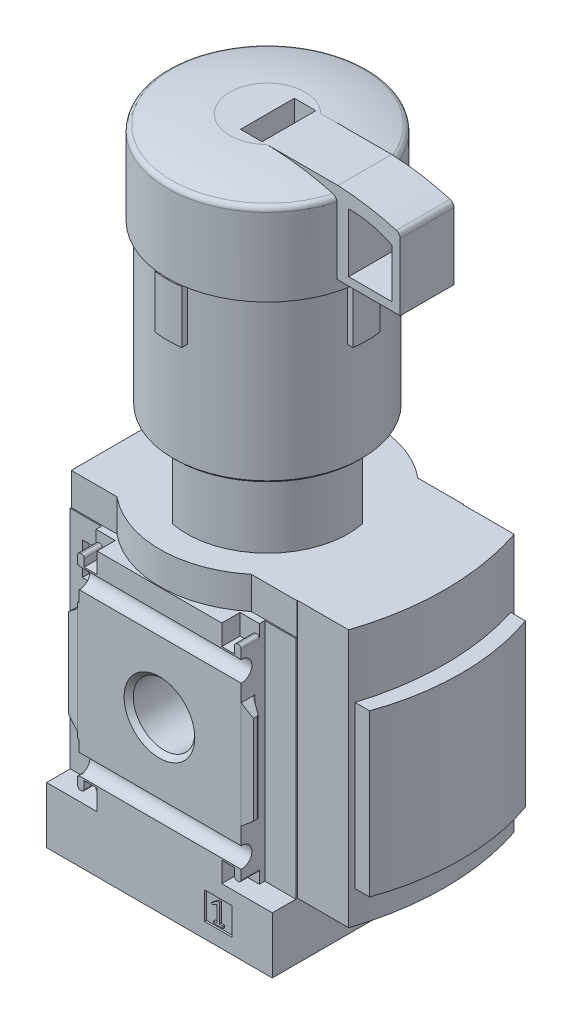
SolidWorks part; units mm, degrees
ref_plane "Front Plane" through (0, 0, 0) normal (0, 0, 1) x (1, 0, 0)
ref_plane "Top Plane" through (0, 0, 0) normal (0, 1, 0) x (1, 0, 0)
ref_plane "Right Plane" through (0, 0, 0) normal (1, 0, 0) x (0, 0, -1)
ref_plane "Plane1" through (0, 27, 0) normal (0, 1, 0) x (1, 0, 0)
sketch "Sketch1" plane through (0, 27, 0) normal (0, 1, 0) x (1, 0, 0)
  line L0 (-21, -15.5) -> (-12.5, -15.5)
  line L1 (12.5, -15.5) -> (21, -15.5)
  line L2 (21, -15.5) -> (21, 15.5)
  line L3 (21, 15.5) -> (12.5, 15.5)
  line L4 (-12.5, 15.5) -> (-21, 15.5)
  line L5 (-21, 15.5) -> (-21, -15.5)
  arc A0 (-12.5, -15.5) -> (12.5, -15.5) centre (0, -0.3889) ccw
  arc A1 (12.5, 15.5) -> (-12.5, 15.5) centre (0, 0.3889) ccw
extrude "Boss-Extrude1" add sketch "Sketch1" against normal blind 48
sketch "Sketch2" plane through (0, 0, 0) normal (0, 0, 1) x (1, 0, 0)
  line L0 (-21, -21) -> (21, -21)
  line L1 (21, -21) -> (21, 21)
  line L2 (21, 21) -> (-21, 21)
  line L3 (-21, 21) -> (-21, -21)
extrude "Boss-Extrude2" add sketch "Sketch2" against normal blind 20.1 and the other way blind 20.1
ref_plane "Plane2" through (0, -31, 0) normal (0, 1, 0) x (1, 0, 0)
ref_plane "Plane3" through (0, -31.5, 0) normal (0, 1, 0) x (1, 0, 0)
sketch "Sketch3" plane through (0, -31.5, 0) normal (0, 1, 0) x (1, 0, 0)
  line L0 (-21, -20.1) -> (21, -20.1)
  line L1 (21, -20.1) -> (21, 20.1)
  line L2 (21, 20.1) -> (-21, 20.1)
  line L3 (-21, 20.1) -> (-21, -20.1)
extrude "Boss-Extrude3" add sketch "Sketch3" along normal blind 10.5
ref_plane "Plane4" through (0, 27, 0) normal (0, 1, 0) x (1, 0, 0)
sketch "Sketch4" plane through (0, 0, 0) normal (1, 0, 0) x (0, 0, -1)
  line L0 (0, 87.2) -> (7, 87.2)
  line L1 (18.6, 84.4576) -> (18.6, 70)
  line L2 (18.6, 70) -> (17.6, 70)
  line L3 (17.6, 70) -> (17.6, 40.5)
  line L4 (17.6, 40.5) -> (17.1, 40)
  line L5 (17.1, 40) -> (15, 40)
  line L6 (15, 40) -> (15, 27)
  line L7 (15, 27) -> (0, 27)
  line L8 (0, 27) -> (0, 87.2)
  line L9 (0, 27) -> (0, 87.2) construction
  arc A0 (7, 87.2) -> (17.8814, 85.4172) centre (5.2199, 42.2352) cw
  arc A1 (17.8814, 85.4172) -> (18.6, 84.4576) centre (17.6, 84.4576) cw
revolve "Revolve1" add sketch "Sketch4" angle 360 about L9 reverse direction yes
cosmetic thread "Cosmetic Thread1" parameters "D1"=13, "D2"=28.16
ref_plane "Plane5" through (0, 103.4, 0) normal (0, 1, 0) x (1, 0, 0)
ref_plane "Plane6" through (0, -94, 0) normal (0, 1, 0) x (1, 0, 0)
ref_plane "Plane7" through (0, 0, -3) normal (0, 0, 1) x (1, 0, 0)
ref_plane "Plane8" through (0, 27, 0) normal (0, 1, 0) x (1, 0, 0)
sketch "Sketch5" plane through (0, 27, 0) normal (0, 1, 0) x (1, 0, 0)
  line L0 (20.9, -15.4) -> (30.5, -15.4)
  line L1 (30.5, 15.4) -> (20.9, 15.4)
  line L2 (20.9, 15.4) -> (20.9, -15.4)
  arc A0 (30.5, -15.4) -> (30.5, 15.4) centre (-15.682, 0) ccw
extrude "Boss-Extrude4" add sketch "Sketch5" against normal blind 48
ref_plane "Plane9" through (0, 15, 0) normal (0, 1, 0) x (1, 0, 0)
sketch "Sketch6" plane through (0, 15, 0) normal (0, 1, 0) x (1, 0, 0)
  line L0 (26, 14.5) -> (26, -14.5)
  line L1 (26, -14.5) -> (33.5, -14.5)
  line L2 (33.5, 14.5) -> (26, 14.5)
  arc A0 (33.5, -14.5) -> (33.5, 14.5) centre (-7.3, 0) ccw
extrude "Boss-Extrude5" add sketch "Sketch6" against normal blind 30
ref_plane "Plane10" through (0, 60, 0) normal (0, 1, 0) x (1, 0, 0)
sketch "Sketch7" plane through (0, 60, 0) normal (0, 1, 0) x (1, 0, 0)
  line L0 (-18.4312, -2.5) -> (-2.5, -2.5)
  line L1 (-2.5, -2.5) -> (-2.5, -18.4312)
  line L2 (2.5, -18.4312) -> (2.5, -2.5)
  line L3 (2.5, -2.5) -> (18.4312, -2.5)
  line L4 (18.4312, 2.5) -> (2.5, 2.5)
  line L5 (2.5, 2.5) -> (2.5, 18.4312)
  line L6 (-2.5, 18.4312) -> (-2.5, 2.5)
  line L7 (-2.5, 2.5) -> (-18.4312, 2.5)
  arc A0 (-18.4312, 2.5) -> (-18.4312, -2.5) centre (0, 0) ccw
  arc A1 (-2.5, -18.4312) -> (2.5, -18.4312) centre (0, 0) ccw
  arc A2 (18.4312, -2.5) -> (18.4312, 2.5) centre (0, 0) ccw
  arc A3 (2.5, 18.4312) -> (-2.5, 18.4312) centre (0, 0) ccw
extrude "Boss-Extrude6" add sketch "Sketch7" along normal blind 9.8
ref_plane "Plane11" through (0, 29, 0) normal (0, 1, 0) x (1, 0, 0)
ref_plane "Plane12" through (0, 79.36, 0) normal (0, 1, 0) x (1, 0, 0)
ref_plane "Plane13" through (0, 82.2, 0) normal (0, 1, 0) x (1, 0, 0)
ref_plane "Plane14" through (0, 77.53, 0) normal (0, 1, 0) x (1, 0, 0)
ref_plane "Plane15" through (0, 80.5, 0) normal (0, 1, 0) x (1, 0, 0)
ref_plane "Plane16" through (0, 87.2, 0) normal (0, 1, 0) x (1, 0, 0)
ref_plane "Plane17" through (0, 0, 20.1) normal (0, 0, 1) x (1, 0, 0)
ref_plane "Plane18" through (0, 0, -20.1) normal (0, 0, 1) x (1, 0, 0)
ref_plane "Plane19" through (0, 27, 0) normal (0, 1, 0) x (1, 0, 0)
sketch "Sketch8" plane through (0, 0, 0) normal (1, 0, 0) x (0, 0, -1)
  line L0 (-20.1, 0) -> (-20.1, 6.5785)
  line L1 (-20.1, 6.5785) -> (-19.244, 5.7225)
  line L2 (-19.244, 5.7225) -> (-7.799, 5.7225)
  line L3 (-7.799, 5.7225) -> (-6.943, 6.5785)
  line L4 (-6.943, 6.5785) -> (-6.943, 0)
  line L5 (-6.943, 0) -> (-20.1, 0)
  line L6 (-6.943, 0) -> (-20.1, 0) construction
revolve "Cut-Revolve1" cut sketch "Sketch8" angle 360 about L6 reverse direction yes
cosmetic thread "Cosmetic Thread2" parameters "D1"=13.157, "D2"=13.157
sketch "Sketch9" plane through (0, 0, 0) normal (1, 0, 0) x (0, 0, -1)
  line L0 (6.943, 0) -> (6.943, 6.5785)
  line L1 (6.943, 6.5785) -> (7.799, 5.7225)
  line L2 (7.799, 5.7225) -> (19.244, 5.7225)
  line L3 (19.244, 5.7225) -> (20.1, 6.5785)
  line L4 (20.1, 6.5785) -> (20.1, 0)
  line L5 (20.1, 0) -> (6.943, 0)
  line L6 (20.1, 0) -> (6.943, 0) construction
revolve "Cut-Revolve2" cut sketch "Sketch9" angle 360 about L6 reverse direction yes
ref_plane "Plane20" through (0, 0, 20.1) normal (0, 0, 1) x (1, 0, 0)
ref_plane "Plane21" through (0, 0, -20.1) normal (0, 0, 1) x (1, 0, 0)
sketch "Sketch10" plane through (0, 0, 20.1) normal (0, 0, 1) x (1, 0, 0)
  line L0 (8.4, -23.59) -> (8.4, -28.69)
  line L1 (8.4, -28.69) -> (13.5, -28.69)
  line L2 (13.5, -28.69) -> (13.5, -23.59)
  line L3 (13.5, -23.59) -> (8.4, -23.59)
  line L4 (9.6632, -25.02) -> (9.7613, -25.2755)
  line L5 (9.7613, -25.2755) -> (10.24, -25.0624)
  line L6 (10.24, -25.0624) -> (10.71, -24.78)
  line L7 (10.71, -24.78) -> (10.71, -27.76)
  line L8 (10.71, -27.76) -> (10.1, -27.76)
  line L9 (10.1, -27.76) -> (10.1, -28.14)
  line L10 (10.1, -28.14) -> (11.8, -28.14)
  line L11 (11.8, -28.14) -> (11.8, -27.76)
  line L12 (11.8, -27.76) -> (11.19, -27.76)
  line L13 (11.19, -27.76) -> (11.19, -24.21)
  line L14 (11.19, -24.21) -> (10.82, -24.21)
  line L15 (10.82, -24.21) -> (9.6632, -25.02)
extrude "Cut-Extrude1" cut sketch "Sketch10" against normal blind 0.35
sketch "Sketch11" plane through (0, 0, -20.1) normal (0, 0, 1) x (1, 0, 0)
  line L0 (-13.5, -23.59) -> (-13.5, -28.69)
  line L1 (-13.5, -28.69) -> (-8.4, -28.69)
  line L2 (-8.4, -28.69) -> (-8.4, -23.59)
  line L3 (-8.4, -23.59) -> (-13.5, -23.59)
  line L4 (-12.0398, -25.2415) -> (-10.4706, -27.4826)
  line L5 (-10.5525, -27.64) -> (-12.15, -27.64)
  line L6 (-12.15, -27.64) -> (-12.15, -28.14)
  line L7 (-12.15, -28.14) -> (-9.75, -28.14)
  line L8 (-9.75, -28.14) -> (-9.75, -27.64)
  line L9 (-9.75, -27.64) -> (-11.5752, -25.0334)
  line L10 (-11.3704, -24.64) -> (-10.75, -24.64)
  line L11 (-10.25, -25.14) -> (-9.75, -25.14)
  line L12 (-10.75, -24.14) -> (-11.4664, -24.14)
  arc A0 (-11.4664, -24.14) -> (-12.0398, -25.2415) centre (-11.4664, -24.84) ccw
  arc A1 (-10.4706, -27.4826) -> (-10.5525, -27.64) centre (-10.5525, -27.54) cw
  arc A2 (-11.5752, -25.0334) -> (-11.3704, -24.64) centre (-11.3704, -24.89) cw
  arc A3 (-10.75, -24.64) -> (-10.25, -25.14) centre (-10.75, -25.14) cw
  arc A4 (-9.75, -25.14) -> (-10.75, -24.14) centre (-10.75, -25.14) ccw
extrude "Cut-Extrude2" cut sketch "Sketch11" along normal blind 0.35
ref_plane "Plane22" through (37.5, 0, 0) normal (1, 0, 0) x (0, 0, -1)
ref_plane "Plane23" through (-44, 0, 0) normal (1, 0, 0) x (0, 0, -1)
ref_plane "Plane24" through (-44.2, 0, 0) normal (1, 0, 0) x (0, 0, -1)
ref_plane "Plane25" through (-44, 0, 0) normal (1, 0, 0) x (0, 0, -1)
sketch "Sketch12" plane through (0, 0, 0) normal (1, 0, 0) x (0, 0, -1)
  line L0 (21.9, -15) -> (21.9, 15)
  line L1 (20.5, 13.167) -> (20.5, -13.167)
  arc A0 (20.5, -13.167) -> (21.9, -15) centre (20, -15) ccw
  arc A1 (21.9, 15) -> (20.5, 13.167) centre (20, 15) ccw
extrude "Cut-Extrude3" cut sketch "Sketch12" along normal blind 25 and the other way blind 25
sketch "Sketch13" plane through (0, 0, 0) normal (1, 0, 0) x (0, 0, -1)
  line L0 (-21.9, 15) -> (-21.9, -15)
  line L1 (-20.5, -13.167) -> (-20.5, 13.167)
  arc A0 (-21.9, -15) -> (-20.5, -13.167) centre (-20, -15) ccw
  arc A1 (-20.5, 13.167) -> (-21.9, 15) centre (-20, 15) ccw
extrude "Cut-Extrude4" cut sketch "Sketch13" along normal blind 25 and the other way blind 25
ref_plane "Plane26" through (-39, 0, 0) normal (1, 0, 0) x (0, 0, -1)
ref_plane "Plane27" through (0, -37.4, 0) normal (0, 1, 0) x (1, 0, 0)
sketch "Sketch14" plane through (0, -37.4, 0) normal (0, 1, 0) x (1, 0, 0)
  line L0 (-9.565, -0.433) -> (-5.1575, -8.067)
  line L1 (-5.1575, -8.067) -> (-4.4075, -8.5)
  line L2 (-4.4075, -8.5) -> (4.4075, -8.5)
  line L3 (4.4075, -8.5) -> (5.1575, -8.067)
  line L4 (5.1575, -8.067) -> (9.565, -0.433)
  line L5 (9.565, -0.433) -> (9.565, 0.433)
  line L6 (9.565, 0.433) -> (5.1575, 8.067)
  line L7 (5.1575, 8.067) -> (4.4075, 8.5)
  line L8 (4.4075, 8.5) -> (-4.4075, 8.5)
  line L9 (-4.4075, 8.5) -> (-5.1575, 8.067)
  line L10 (-5.1575, 8.067) -> (-9.565, 0.433)
  line L11 (-9.565, 0.433) -> (-9.565, -0.433)
extrude "Boss-Extrude7" add sketch "Sketch14" along normal blind 6.5
sketch "Sketch15" plane through (0, -37.4, 0) normal (0, 1, 0) x (1, 0, 0)
  line L0 (-5.1962, 0) -> (-2.5981, -4.5)
  line L1 (-2.5981, -4.5) -> (2.5981, -4.5)
  line L2 (2.5981, -4.5) -> (5.1962, 0)
  line L3 (5.1962, 0) -> (2.5981, 4.5)
  line L4 (2.5981, 4.5) -> (-2.5981, 4.5)
  line L5 (-2.5981, 4.5) -> (-5.1962, 0)
extrude "Cut-Extrude5" cut sketch "Sketch15" along normal blind 8.3
ref_plane "Plane28" through (0, 0, 20.1) normal (0, 0, 1) x (1, 0, 0)
ref_plane "Plane29" through (0, 0, -20.1) normal (0, 0, 1) x (1, 0, 0)
sketch "Sketch16" plane through (0, 0, 20.1) normal (0, 0, 1) x (1, 0, 0)
  line L0 (11.6, 21) -> (11.6, 17.2)
  line L1 (11.6, 17.2) -> (14, 17.2)
  line L2 (14, 17.2) -> (14, 18.6)
  line L3 (14.5, 19.1) -> (14.7, 19.1)
  line L4 (15.2, 18.6) -> (15.2, 9.95)
  line L5 (15.2, 9.95) -> (21.5, 4.6637)
  line L6 (21.5, 4.6637) -> (21.5, -4.6637)
  line L7 (21.5, -4.6637) -> (15.2, -9.95)
  line L8 (15.2, -9.95) -> (15.2, -18.6)
  line L9 (14.7, -19.1) -> (14.5, -19.1)
  line L10 (14, -18.6) -> (14, -17.2)
  line L11 (14, -17.2) -> (11.6, -17.2)
  line L12 (11.6, -17.2) -> (11.6, -21)
  line L13 (11.6, -21) -> (22, -21)
  line L14 (22, -21) -> (22, 21)
  line L15 (22, 21) -> (11.6, 21)
  arc A0 (14, 18.6) -> (14.5, 19.1) centre (14.5, 18.6) cw
  arc A1 (14.7, 19.1) -> (15.2, 18.6) centre (14.7, 18.6) cw
  arc A2 (15.2, -18.6) -> (14.7, -19.1) centre (14.7, -18.6) cw
  arc A3 (14.5, -19.1) -> (14, -18.6) centre (14.5, -18.6) cw
extrude "Cut-Extrude6" cut sketch "Sketch16" along normal blind 3.4 and the other way blind 3.4
sketch "Sketch17" plane through (0, 0, 20.1) normal (0, 0, 1) x (1, 0, 0)
  line L0 (-22, -21) -> (-11.6, -21)
  line L1 (-11.6, -21) -> (-11.6, -17.2)
  line L2 (-11.6, -17.2) -> (-14, -17.2)
  line L3 (-14, -17.2) -> (-14, -18.6)
  line L4 (-14.5, -19.1) -> (-14.7, -19.1)
  line L5 (-15.2, -18.6) -> (-15.2, -9.95)
  line L6 (-15.2, -9.95) -> (-21.5, -4.6637)
  line L7 (-21.5, -4.6637) -> (-21.5, 4.6637)
  line L8 (-21.5, 4.6637) -> (-15.2, 9.95)
  line L9 (-15.2, 9.95) -> (-15.2, 18.6)
  line L10 (-14.7, 19.1) -> (-14.5, 19.1)
  line L11 (-14, 18.6) -> (-14, 17.2)
  line L12 (-14, 17.2) -> (-11.6, 17.2)
  line L13 (-11.6, 17.2) -> (-11.6, 21)
  line L14 (-11.6, 21) -> (-22, 21)
  line L15 (-22, 21) -> (-22, -21)
  arc A0 (-14, -18.6) -> (-14.5, -19.1) centre (-14.5, -18.6) cw
  arc A1 (-14.7, -19.1) -> (-15.2, -18.6) centre (-14.7, -18.6) cw
  arc A2 (-15.2, 18.6) -> (-14.7, 19.1) centre (-14.7, 18.6) cw
  arc A3 (-14.5, 19.1) -> (-14, 18.6) centre (-14.5, 18.6) cw
extrude "Cut-Extrude7" cut sketch "Sketch17" along normal blind 3.4 and the other way blind 3.4
sketch "Sketch18" plane through (0, 0, -20.1) normal (0, 0, 1) x (1, 0, 0)
  line L0 (11.6, 21) -> (11.6, 17.2)
  line L1 (11.6, 17.2) -> (14, 17.2)
  line L2 (14, 17.2) -> (14, 18.6)
  line L3 (14.5, 19.1) -> (14.7, 19.1)
  line L4 (15.2, 18.6) -> (15.2, 9.95)
  line L5 (15.2, 9.95) -> (21.5, 4.6637)
  line L6 (21.5, 4.6637) -> (21.5, -4.6637)
  line L7 (21.5, -4.6637) -> (15.2, -9.95)
  line L8 (15.2, -9.95) -> (15.2, -18.6)
  line L9 (14.7, -19.1) -> (14.5, -19.1)
  line L10 (14, -18.6) -> (14, -17.2)
  line L11 (14, -17.2) -> (11.6, -17.2)
  line L12 (11.6, -17.2) -> (11.6, -21)
  line L13 (11.6, -21) -> (22, -21)
  line L14 (22, -21) -> (22, 21)
  line L15 (22, 21) -> (11.6, 21)
  arc A0 (14, 18.6) -> (14.5, 19.1) centre (14.5, 18.6) cw
  arc A1 (14.7, 19.1) -> (15.2, 18.6) centre (14.7, 18.6) cw
  arc A2 (15.2, -18.6) -> (14.7, -19.1) centre (14.7, -18.6) cw
  arc A3 (14.5, -19.1) -> (14, -18.6) centre (14.5, -18.6) cw
extrude "Cut-Extrude8" cut sketch "Sketch18" along normal blind 3.4 and the other way blind 3.4
sketch "Sketch19" plane through (0, 0, -20.1) normal (0, 0, 1) x (1, 0, 0)
  line L0 (-22, -21) -> (-11.6, -21)
  line L1 (-11.6, -21) -> (-11.6, -17.2)
  line L2 (-11.6, -17.2) -> (-14, -17.2)
  line L3 (-14, -17.2) -> (-14, -18.6)
  line L4 (-14.5, -19.1) -> (-14.7, -19.1)
  line L5 (-15.2, -18.6) -> (-15.2, -9.95)
  line L6 (-15.2, -9.95) -> (-21.5, -4.6637)
  line L7 (-21.5, -4.6637) -> (-21.5, 4.6637)
  line L8 (-21.5, 4.6637) -> (-15.2, 9.95)
  line L9 (-15.2, 9.95) -> (-15.2, 18.6)
  line L10 (-14.7, 19.1) -> (-14.5, 19.1)
  line L11 (-14, 18.6) -> (-14, 17.2)
  line L12 (-14, 17.2) -> (-11.6, 17.2)
  line L13 (-11.6, 17.2) -> (-11.6, 21)
  line L14 (-11.6, 21) -> (-22, 21)
  line L15 (-22, 21) -> (-22, -21)
  arc A0 (-14, -18.6) -> (-14.5, -19.1) centre (-14.5, -18.6) cw
  arc A1 (-14.7, -19.1) -> (-15.2, -18.6) centre (-14.7, -18.6) cw
  arc A2 (-15.2, 18.6) -> (-14.7, 19.1) centre (-14.7, 18.6) cw
  arc A3 (-14.5, 19.1) -> (-14, 18.6) centre (-14.5, 18.6) cw
extrude "Cut-Extrude9" cut sketch "Sketch19" along normal blind 3.4 and the other way blind 3.4
sketch "Sketch20" plane through (0, 0, 0) normal (0, 1, 0) x (1, 0, 0)
  line L0 (-22.2, 25.1) -> (-22.2, 15.7)
  line L1 (-22.2, 15.7) -> (-15.2, 15.7)
  line L2 (-15.2, 15.7) -> (-15.2, 17.4001)
  line L3 (-15.6493, 18.1191) -> (-16.9192, 18.7385)
  line L4 (-17.2, 19.1879) -> (-17.2, 19.8)
  line L5 (-17.2, 19.8) -> (-15.2, 20.1)
  line L6 (-15.2, 20.1) -> (15.2, 20.1)
  line L7 (15.2, 20.1) -> (17.2, 19.8)
  line L8 (17.2, 19.8) -> (17.2, 19.1879)
  line L9 (16.9192, 18.7385) -> (15.6493, 18.1191)
  line L10 (15.2, 17.4001) -> (15.2, 15.7)
  line L11 (15.2, 15.7) -> (22.2, 15.7)
  line L12 (22.2, 15.7) -> (22.2, 25.1)
  line L13 (22.2, 25.1) -> (-22.2, 25.1)
  arc A0 (-15.2, 17.4001) -> (-15.6493, 18.1191) centre (-16, 17.4001) ccw
  arc A1 (-16.9192, 18.7385) -> (-17.2, 19.1879) centre (-16.7, 19.1879) cw
  arc A2 (17.2, 19.1879) -> (16.9192, 18.7385) centre (16.7, 19.1879) cw
  arc A3 (15.6493, 18.1191) -> (15.2, 17.4001) centre (16, 17.4001) ccw
extrude "Cut-Extrude10" cut sketch "Sketch20" along normal blind 21 and the other way blind 21
sketch "Sketch21" plane through (0, 0, 0) normal (0, 1, 0) x (1, 0, 0)
  line L0 (-22.2, -15.7) -> (-22.2, -25.1)
  line L1 (-22.2, -25.1) -> (22.2, -25.1)
  line L2 (22.2, -25.1) -> (22.2, -15.7)
  line L3 (22.2, -15.7) -> (15.2, -15.7)
  line L4 (15.2, -15.7) -> (15.2, -17.4001)
  line L5 (15.6493, -18.1191) -> (16.9192, -18.7385)
  line L6 (17.2, -19.1879) -> (17.2, -19.8)
  line L7 (17.2, -19.8) -> (15.2, -20.1)
  line L8 (15.2, -20.1) -> (-15.2, -20.1)
  line L9 (-15.2, -20.1) -> (-17.2, -19.8)
  line L10 (-17.2, -19.8) -> (-17.2, -19.1879)
  line L11 (-16.9192, -18.7385) -> (-15.6493, -18.1191)
  line L12 (-15.2, -17.4001) -> (-15.2, -15.7)
  line L13 (-15.2, -15.7) -> (-22.2, -15.7)
  arc A0 (15.2, -17.4001) -> (15.6493, -18.1191) centre (16, -17.4001) ccw
  arc A1 (16.9192, -18.7385) -> (17.2, -19.1879) centre (16.7, -19.1879) cw
  arc A2 (-17.2, -19.1879) -> (-16.9192, -18.7385) centre (-16.7, -19.1879) cw
  arc A3 (-15.6493, -18.1191) -> (-15.2, -17.4001) centre (-16, -17.4001) ccw
extrude "Cut-Extrude11" cut sketch "Sketch21" along normal blind 21 and the other way blind 21
ref_plane "Plane30" through (-27.8, 0, 0) normal (1, 0, 0) x (0, 0, -1)
ref_plane "Plane31" through (0, 0, 1) normal (0, 0, 1) x (1, 0, 0)
sketch "Sketch22" plane through (0, 87.2, 0) normal (0, 1, 0) x (1, 0, 0)
  line L0 (0, 5) -> (0, -5)
  line L1 (0, -5) -> (20, -5)
  line L2 (20, -5) -> (20, 5)
  line L3 (20, 5) -> (0, 5)
extrude "Cut-Extrude12" cut sketch "Sketch22" against normal blind 15
sketch "Sketch23" plane through (0, 0, 0) normal (0, 0, 1) x (1, 0, 0)
  line L0 (4, 72) -> (29.7, 72)
  line L1 (29.7, 72) -> (29.7, 84.4576)
  line L2 (18.1, 87.2) -> (4, 87.2)
  line L3 (4, 87.2) -> (4, 72)
  line L4 (20.1, 84.4576) -> (20.1, 73.5)
  line L5 (20.1, 73.5) -> (28.2, 73.5)
  line L6 (28.2, 73.5) -> (28.2, 82.6)
  arc A0 (29.7, 84.4576) -> (28.9814, 85.4172) centre (28.7, 84.4576) ccw
  arc A1 (28.9814, 85.4172) -> (18.1, 87.2) centre (16.3199, 42.2352) ccw
  arc A2 (28.2, 82.6) -> (20.1, 84.4576) centre (20.235, 66.4581) ccw
extrude "Boss-Extrude8" add sketch "Sketch23" against normal blind 5 and the other way blind 5
ref_plane "Plane32" through (15.5, 0, 0) normal (1, 0, 0) x (0, 0, -1)
ref_plane "Plane33" through (-15.5, 0, 0) normal (1, 0, 0) x (0, 0, -1)
ref_plane "Plane34" through (0, 0, 20.1) normal (0, 0, 1) x (1, 0, 0)
ref_plane "Plane35" through (0, 0, -20.1) normal (0, 0, 1) x (1, 0, 0)
ref_plane "Plane36" through (-21, 0, 0) normal (1, 0, 0) x (0, 0, -1)
ref_plane "Plane37" through (0, -64, 0) normal (0, 1, 0) x (1, 0, 0)
ref_plane "Plane38" through (0, -31, 0) normal (0, 1, 0) x (1, 0, 0)
ref_plane "Plane39" through (0, -91.2, 0) normal (0, 1, 0) x (1, 0, 0)
ref_plane "Plane40" through (21, 0, 0) normal (1, 0, 0) x (0, 0, -1)
ref_plane "Plane41" through (0, 27, 0) normal (0, 1, 0) x (1, 0, 0)
sketch "Sketch24" plane through (0, 27, 0) normal (0, 1, 0) x (1, 0, 0)
  line L0 (-49.4975, 7.0711) -> (7.0711, -49.4975)
  line L1 (7.0711, -49.4975) -> (49.4975, -7.0711)
  line L2 (49.4975, -7.0711) -> (-7.0711, 49.4975)
  line L3 (-7.0711, 49.4975) -> (-49.4975, 7.0711)
  line L4 (-30.052, 12.3744) -> (12.3744, -30.052)
  line L5 (12.3744, -30.052) -> (30.052, -12.3744)
  line L6 (30.052, -12.3744) -> (-12.3744, 30.052)
  line L7 (-12.3744, 30.052) -> (-30.052, 12.3744)
extrude "Cut-Extrude13" cut sketch "Sketch24" along normal blind 13
ref_plane "Plane42" through (0, 29, 0) normal (0, 1, 0) x (1, 0, 0)
sketch "Sketch25" plane through (0, 0, 0) normal (0, 0, 1) x (1, 0, 0)
  line L0 (-18.73, 10.97) -> (-14.92, 10.97)
  line L1 (-14.92, 10.97) -> (-14.92, 17.04)
  line L2 (-14.92, 17.04) -> (-18.73, 17.04)
  line L3 (-18.73, 17.04) -> (-18.73, 10.97)
extrude "Cut-Extrude14" cut sketch "Sketch25" along normal blind 22 and the other way blind 22
sketch "Sketch26" plane through (0, 0, 0) normal (0, 0, 1) x (1, 0, 0)
  line L0 (-18.73, -17.03) -> (-14.92, -17.03)
  line L1 (-14.92, -17.03) -> (-14.92, -10.96)
  line L2 (-14.92, -10.96) -> (-18.73, -10.96)
  line L3 (-18.73, -10.96) -> (-18.73, -17.03)
extrude "Cut-Extrude15" cut sketch "Sketch26" along normal blind 22 and the other way blind 22
ref_plane "Plane43" through (-21, 0, 0) normal (1, 0, 0) x (0, 0, -1)
sketch "Sketch27" plane through (-21, 0, 0) normal (1, 0, 0) x (0, 0, -1)
  line L0 (-14.5, -18.95) -> (14.5, -18.95)
  line L1 (14.5, -18.95) -> (14.5, 18.95)
  line L2 (14.5, 18.95) -> (-14.5, 18.95)
  line L3 (-14.5, 18.95) -> (-14.5, -18.95)
extrude "Cut-Extrude16" cut sketch "Sketch27" along normal blind 11 and the other way blind 11
sketch "Sketch28" plane through (0, 0, 0) normal (0, 1, 0) x (1, 0, 0)
  line L0 (-11.4891, -14.5) -> (-10, -14.5)
  line L1 (-10, -14.5) -> (-10, 14.5)
  line L2 (-10, 14.5) -> (-11.4891, 14.5)
  arc A0 (-11.4891, 14.5) -> (-11.4891, -14.5) centre (0, 0) ccw
extrude "Boss-Extrude9" add sketch "Sketch28" against normal blind 19 and the other way blind 19
ref_plane "Plane44" through (-19.9, 0, 0) normal (1, 0, 0) x (0, 0, -1)
sketch "Sketch29" plane through (-19.9, 0, 0) normal (1, 0, 0) x (0, 0, -1)
  line L0 (8.8, -21.3) -> (14.6, -21.3)
  line L1 (14.6, -21.3) -> (14.6, -17.1)
  line L2 (14.6, -17.1) -> (13.1633, -17.1)
  line L3 (8.8, -17.5) -> (8.8, -21.3)
  arc A0 (13.1633, -17.1) -> (8.8, -17.5) centre (11, -17.5) ccw
extrude "Boss-Extrude10" add sketch "Sketch29" along normal blind 9
sketch "Sketch30" plane through (-19.9, 0, 0) normal (1, 0, 0) x (0, 0, -1)
  line L0 (-14.6, 17.1) -> (-13.1633, 17.1)
  line L1 (-8.8, 17.5) -> (-8.8, 21.3)
  line L2 (-8.8, 21.3) -> (-14.6, 21.3)
  line L3 (-14.6, 21.3) -> (-14.6, 17.1)
  arc A0 (-13.1633, 17.1) -> (-8.8, 17.5) centre (-11, 17.5) ccw
extrude "Boss-Extrude11" add sketch "Sketch30" along normal blind 9
ref_plane "Plane45" through (-18, 0, 0) normal (1, 0, 0) x (0, 0, -1)
sketch "Sketch31" plane through (-18, 0, 0) normal (1, 0, 0) x (0, 0, -1)
  circle A0 centre (8.6, 6) radius 3.05
extrude "Boss-Extrude12" add sketch "Sketch31" along normal blind 4
ref_plane "ABDECKUNG XY" through (-21, 0, 0) normal (1, 0, 0) x (0, 0, -1)
ref_plane "ABDECKUNG XZ" through (0, 0, 0) normal (0, -1, 0) x (-1, 0, 0)
ref_plane "ABDECKUNG YZ" through (0, 0, 0) normal (0, 0, -1) x (-1, 0, 0)
ref_axis "ABDECKUNG X" through (-21, 0, 80.9) along (0, 0, -1)
ref_axis "ABDECKUNG Y" through (-21, -50, 0) along (0, 1, 0)
ref_axis "ABDECKUNG Z" through (80.9, 0, 0) along (-1, 0, 0)
sketch3d "ABDECKUNG"
  point P0 (-21, 0, 0)
ref_plane "IP_LINKS XY" through (0, 0, 20.1) normal (0, 0, 1) x (1, 0, 0)
ref_plane "IP_LINKS XZ" through (0, 0, 0) normal (0, -1, 0) x (-1, 0, 0)
ref_plane "IP_LINKS YZ" through (0, 0, 0) normal (1, 0, 0) x (0, 0, -1)
ref_axis "IP_LINKS X" through (-80.9, 0, 20.1) along (1, 0, 0)
ref_axis "IP_LINKS Y" through (0, -50, 20.1) along (0, 1, 0)
ref_axis "IP_LINKS Z" through (0, 0, 80.9) along (0, 0, -1)
sketch3d "IP_LINKS"
  point P0 (0, 0, 20.1)
ref_plane "IP_MANOMETER XY" through (37.5, 0, 0) normal (1, 0, 0) x (0, 0, -1)
ref_plane "IP_MANOMETER XZ" through (0, 0, 0) normal (0, -1, 0) x (-1, 0, 0)
ref_plane "IP_MANOMETER YZ" through (0, 0, 0) normal (0, 0, -1) x (-1, 0, 0)
ref_axis "IP_MANOMETER X" through (37.5, 0, 80.9) along (0, 0, -1)
ref_axis "IP_MANOMETER Y" through (37.5, -50, 0) along (0, 1, 0)
ref_axis "IP_MANOMETER Z" through (80.9, 0, 0) along (-1, 0, 0)
sketch3d "IP_MANOMETER"
  point P0 (37.5, 0, 0)
ref_plane "IP_MUTTER XY" through (0, 27, 0) normal (0, 1, 0) x (1, 0, 0)
ref_plane "IP_MUTTER XZ" through (0, 0, 0) normal (0, 0, 1) x (1, 0, 0)
ref_plane "IP_MUTTER YZ" through (0, 0, 0) normal (1, 0, 0) x (0, 0, -1)
ref_axis "IP_MUTTER X" through (-80.9, 27, 0) along (1, 0, 0)
ref_axis "IP_MUTTER Y" through (0, 27, 50) along (0, 0, -1)
ref_axis "IP_MUTTER Z" through (0, 50, 0) along (0, -1, 0)
sketch3d "IP_MUTTER"
  point P0 (0, 27, 0)
ref_plane "IP_MUTTER_UNTEN XY" through (0, -31, 0) normal (0, 1, 0) x (1, 0, 0)
ref_plane "IP_MUTTER_UNTEN XZ" through (0, 0, 0) normal (0, 0, 1) x (1, 0, 0)
ref_plane "IP_MUTTER_UNTEN YZ" through (0, 0, 0) normal (1, 0, 0) x (0, 0, -1)
ref_axis "IP_MUTTER_UNTEN X" through (-80.9, -31, 0) along (1, 0, 0)
ref_axis "IP_MUTTER_UNTEN Y" through (0, -31, 50) along (0, 0, -1)
ref_axis "IP_MUTTER_UNTEN Z" through (0, 50, 0) along (0, -1, 0)
sketch3d "IP_MUTTER_UNTEN"
  point P0 (0, -31, 0)
ref_plane "IP_PLATTE_HINTEN_1 XY" through (-15.5, 0, 0) normal (1, 0, 0) x (0, 0, -1)
ref_plane "IP_PLATTE_HINTEN_1 XZ" through (0, 0, 0) normal (0, -1, 0) x (-1, 0, 0)
ref_plane "IP_PLATTE_HINTEN_1 YZ" through (0, 0, 20.1) normal (0, 0, -1) x (-1, 0, 0)
ref_axis "IP_PLATTE_HINTEN_1 X" through (-15.5, 0, 80.9) along (0, 0, -1)
ref_axis "IP_PLATTE_HINTEN_1 Y" through (-15.5, -50, 20.1) along (0, 1, 0)
ref_axis "IP_PLATTE_HINTEN_1 Z" through (80.9, 0, 20.1) along (-1, 0, 0)
sketch3d "IP_PLATTE_HINTEN_1"
  point P0 (-15.5, 0, 20.1)
ref_plane "IP_PLATTE_HINTEN_2 XY" through (-15.5, 0, 0) normal (1, 0, 0) x (0, 0, -1)
ref_plane "IP_PLATTE_HINTEN_2 XZ" through (0, 0, 0) normal (0, -1, 0) x (-1, 0, 0)
ref_plane "IP_PLATTE_HINTEN_2 YZ" through (0, 0, -20.1) normal (0, 0, -1) x (-1, 0, 0)
ref_axis "IP_PLATTE_HINTEN_2 X" through (-15.5, 0, 80.9) along (0, 0, -1)
ref_axis "IP_PLATTE_HINTEN_2 Y" through (-15.5, -50, -20.1) along (0, 1, 0)
ref_axis "IP_PLATTE_HINTEN_2 Z" through (80.9, 0, -20.1) along (-1, 0, 0)
sketch3d "IP_PLATTE_HINTEN_2"
  point P0 (-15.5, 0, -20.1)
ref_plane "IP_PLATTE_LINKS XY" through (0, 0, 20.1) normal (0, 0, 1) x (1, 0, 0)
ref_plane "IP_PLATTE_LINKS XZ" through (0, 0, 0) normal (0, -1, 0) x (-1, 0, 0)
ref_plane "IP_PLATTE_LINKS YZ" through (0, 0, 0) normal (1, 0, 0) x (0, 0, -1)
ref_axis "IP_PLATTE_LINKS X" through (-80.9, 0, 20.1) along (1, 0, 0)
ref_axis "IP_PLATTE_LINKS Y" through (0, -50, 20.1) along (0, 1, 0)
ref_axis "IP_PLATTE_LINKS Z" through (0, 0, 80.9) along (0, 0, -1)
sketch3d "IP_PLATTE_LINKS"
  point P0 (0, 0, 20.1)
ref_plane "IP_PLATTE_RECHTS XY" through (0, 0, -20.1) normal (0, 0, 1) x (1, 0, 0)
ref_plane "IP_PLATTE_RECHTS XZ" through (0, 0, 0) normal (0, -1, 0) x (-1, 0, 0)
ref_plane "IP_PLATTE_RECHTS YZ" through (0, 0, 0) normal (1, 0, 0) x (0, 0, -1)
ref_axis "IP_PLATTE_RECHTS X" through (-80.9, 0, -20.1) along (1, 0, 0)
ref_axis "IP_PLATTE_RECHTS Y" through (0, -50, -20.1) along (0, 1, 0)
ref_axis "IP_PLATTE_RECHTS Z" through (0, 0, 80.9) along (0, 0, -1)
sketch3d "IP_PLATTE_RECHTS"
  point P0 (0, 0, -20.1)
ref_plane "IP_PLATTE_VORNE 1 XY" through (15.5, 0, 0) normal (1, 0, 0) x (0, 0, -1)
ref_plane "IP_PLATTE_VORNE 1 XZ" through (0, 0, 0) normal (0, -1, 0) x (-1, 0, 0)
ref_plane "IP_PLATTE_VORNE 1 YZ" through (0, 0, 20.1) normal (0, 0, -1) x (-1, 0, 0)
ref_axis "IP_PLATTE_VORNE 1 X" through (15.5, 0, 80.9) along (0, 0, -1)
ref_axis "IP_PLATTE_VORNE 1 Y" through (15.5, -50, 20.1) along (0, 1, 0)
ref_axis "IP_PLATTE_VORNE 1 Z" through (80.9, 0, 20.1) along (-1, 0, 0)
sketch3d "IP_PLATTE_VORNE 1"
  point P0 (15.5, 0, 20.1)
ref_plane "IP_PLATTE_VORNE 2 XY" through (15.5, 0, 0) normal (1, 0, 0) x (0, 0, -1)
ref_plane "IP_PLATTE_VORNE 2 XZ" through (0, 0, 0) normal (0, -1, 0) x (-1, 0, 0)
ref_plane "IP_PLATTE_VORNE 2 YZ" through (0, 0, -20.1) normal (0, 0, -1) x (-1, 0, 0)
ref_axis "IP_PLATTE_VORNE 2 X" through (15.5, 0, 80.9) along (0, 0, -1)
ref_axis "IP_PLATTE_VORNE 2 Y" through (15.5, -50, -20.1) along (0, 1, 0)
ref_axis "IP_PLATTE_VORNE 2 Z" through (80.9, 0, -20.1) along (-1, 0, 0)
sketch3d "IP_PLATTE_VORNE 2"
  point P0 (15.5, 0, -20.1)
ref_plane "IP_RECHTS XY" through (0, 0, -20.1) normal (0, 0, 1) x (1, 0, 0)
ref_plane "IP_RECHTS XZ" through (0, 0, 0) normal (0, -1, 0) x (-1, 0, 0)
ref_plane "IP_RECHTS YZ" through (0, 0, 0) normal (1, 0, 0) x (0, 0, -1)
ref_axis "IP_RECHTS X" through (-80.9, 0, -20.1) along (1, 0, 0)
ref_axis "IP_RECHTS Y" through (0, -50, -20.1) along (0, 1, 0)
ref_axis "IP_RECHTS Z" through (0, 0, 80.9) along (0, 0, -1)
sketch3d "IP_RECHTS"
  point P0 (0, 0, -20.1)
ref_plane "IP_SDE1 XY" through (21, 0, 0) normal (1, 0, 0) x (0, 0, -1)
ref_plane "IP_SDE1 XZ" through (0, 0, 0) normal (0, -1, 0) x (-1, 0, 0)
ref_plane "IP_SDE1 YZ" through (0, 0, 0) normal (0, 0, -1) x (-1, 0, 0)
ref_axis "IP_SDE1 X" through (21, 0, 80.9) along (0, 0, -1)
ref_axis "IP_SDE1 Y" through (21, -50, 0) along (0, 1, 0)
ref_axis "IP_SDE1 Z" through (80.9, 0, 0) along (-1, 0, 0)
sketch3d "IP_SDE1"
  point P0 (21, 0, 0)
ref_plane "IP_WB XY" through (-21, 0, 0) normal (1, 0, 0) x (0, 0, -1)
ref_plane "IP_WB XZ" through (0, -20.6, 0) normal (0, -1, 0) x (-1, 0, 0)
ref_plane "IP_WB YZ" through (0, 0, 0) normal (0, 0, -1) x (-1, 0, 0)
ref_axis "IP_WB X" through (-21, -20.6, 80.9) along (0, 0, -1)
ref_axis "IP_WB Y" through (-21, -50, 0) along (0, 1, 0)
ref_axis "IP_WB Z" through (80.9, -20.6, 0) along (-1, 0, 0)
sketch3d "IP_WB"
  point P0 (-21, -20.6, 0)
ref_plane "SD5 XY" through (21, 0, 0) normal (1, 0, 0) x (0, 0, -1)
ref_plane "SD5 XZ" through (0, -21.24, 0) normal (0, -1, 0) x (-1, 0, 0)
ref_plane "SD5 YZ" through (0, 0, 0) normal (0, 0, -1) x (-1, 0, 0)
ref_axis "SD5 X" through (21, -21.24, 80.9) along (0, 0, -1)
ref_axis "SD5 Y" through (21, -50, 0) along (0, 1, 0)
ref_axis "SD5 Z" through (80.9, -21.24, 0) along (-1, 0, 0)
sketch3d "SD5"
  point P0 (21, -21.24, 0)
